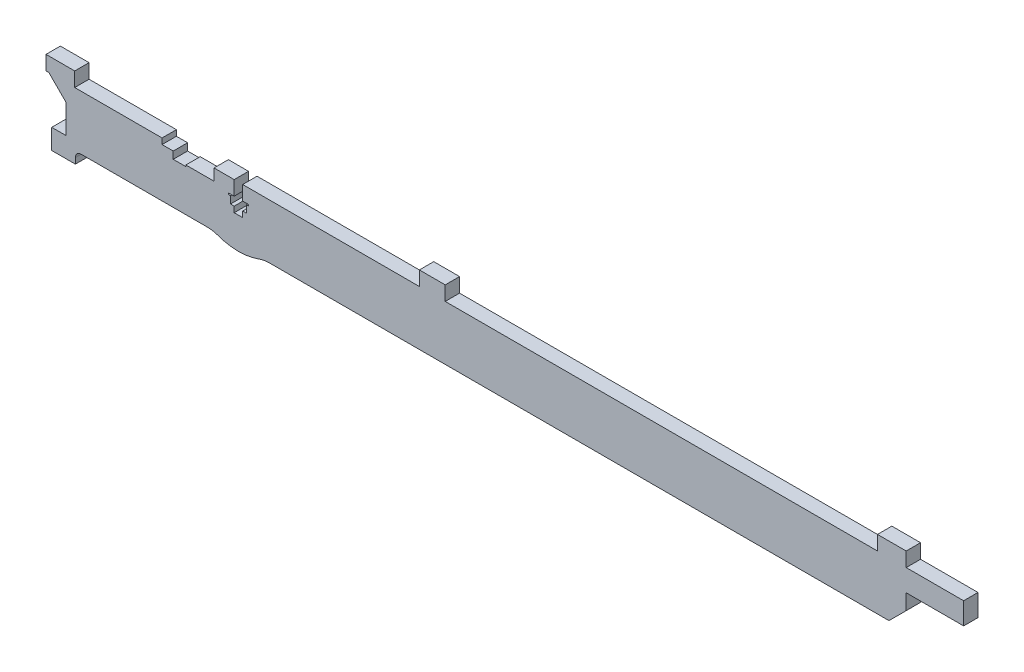
SolidWorks part; units mm, degrees
material "6061-T6 Black anodised"
ref_plane "Front Plane" through (0, 0, 0) normal (0, 0, 1) x (1, 0, 0)
ref_plane "Top Plane" through (0, 0, 0) normal (0, 1, 0) x (1, 0, 0)
ref_plane "Right Plane" through (0, 0, 0) normal (1, 0, 0) x (0, 0, -1)
sketch "Sketch1" plane through (0, 0, 0) normal (0, 0, 1) x (1, 0, 0)
  line L0 (-250.8, 3.6) -> (-241, 3.6)
  line L1 (0, 0) -> (20, 0)
  line L2 (-232.5, 8.6) -> (-232.5, -2.4) construction
  line L3 (0, 7.6) -> (20, 7.6)
  line L4 (20, 0) -> (20, 7.6)
  line L5 (-10, 7.6) -> (-160.5, 7.6)
  line L6 (0, 0) -> (0, -11.4)
  line L7 (0, -11.4) -> (-221.7995, -11.4)
  line L8 (-292.5, 1.6) -> (-292.5, -8.4)
  line L9 (-259.0932, 7.6) -> (-289.5, 7.6)
  line L10 (-299.5, 7.6) -> (-299.5, 12.6)
  line L11 (-299.5, 12.6) -> (-289.5, 12.6)
  line L12 (-289.5, 7.6) -> (-289.5, 12.6)
  line L13 (-169.5, 7.6) -> (-169.5, 12.6)
  line L14 (-250.8, 3.6) -> (-250.8, 3.1)
  line L15 (-250.8, 3.1) -> (-255.2, 3.1)
  line L16 (-255.2, 3.1) -> (-255.2, 5.6)
  line L17 (-255.2, 5.6) -> (-259.0932, 5.6)
  line L18 (0, 7.6) -> (0, 12.6)
  line L19 (0, 12.6) -> (-10, 12.6)
  line L20 (-10, 7.6) -> (-10, 12.6)
  line L21 (-259.0932, 5.6) -> (-259.0932, 7.6)
  line L22 (-255, 3.6) -> (-251, 3.6) construction
  line L23 (-255, 3.6) -> (-255, 13.6) construction
  line L24 (-251, 3.6) -> (-251, 13.6) construction
  line L25 (-255, 13.6) -> (-251, 13.6) construction
  line L26 (-255, 3.6) -> (-251, 13.6) construction
  line L27 (-271, 32.6) -> (-219.2068, 32.6) construction
  line L28 (-271, 32.6) -> (-271, 13.6) construction
  line L29 (-250, 33.6) -> (-250, 13.6) construction
  line L30 (-271, 13.6) -> (-250, 13.6) construction
  line L31 (-271, 32.6) -> (-250, 13.6) construction
  line L32 (-250, 33.6) -> (-271, 13.6) construction
  line L33 (-169.5, 12.6) -> (-160.5, 12.6)
  line L34 (-160.5, 12.6) -> (-160.5, 7.6)
  line L35 (-169.5, 7.6) -> (-231.02, 7.6)
  line L36 (-299.5, 7.6) -> (-298.5, 7.6)
  line L37 (-298.5, 7.6) -> (-292.5, 1.6)
  line L38 (-233.98, 7.6) -> (-233.98, 2.6)
  line L39 (-233.98, 2.6) -> (-236, 2.6)
  line L40 (-236, 2.6) -> (-236, 2.1)
  line L41 (-236, 2.1) -> (-235.25, 2.1)
  line L42 (-235.25, 2.1) -> (-235.25, -0.4)
  line L43 (-235.25, -0.4) -> (-233.98, -0.4)
  line L44 (-233.98, -0.4) -> (-233.98, -2.4)
  line L45 (-233.98, -2.4) -> (-231.02, -2.4)
  line L46 (-233.98, 7.6) -> (-241, 7.6)
  line L47 (-231.02, -0.4) -> (-231.02, -2.4)
  line L48 (-229.75, -0.4) -> (-231.02, -0.4)
  line L49 (-229.75, 2.1) -> (-229.75, -0.4)
  line L50 (-229, 2.1) -> (-229.75, 2.1)
  line L51 (-229, 2.6) -> (-229, 2.1)
  line L52 (-231.02, 2.6) -> (-229, 2.6)
  line L53 (-231.02, 7.6) -> (-231.02, 2.6)
  line L54 (-283, -20.0132) -> (-282, -18.2812)
  line L55 (-243.2005, -11.4) -> (-287.2708, -11.4)
  line L56 (-282, -15.4) -> (-287.2708, -15.4)
  line L57 (-251, 3.6) -> (-255, 13.6) construction
  line L58 (-282, -15.4) -> (-282, -18.2812)
  line L60 (-282, -30.9) -> (-297.5, -30.9)
  line L61 (-297.5, -30.9) -> (-297.5, -8.4)
  line L62 (-297.5, -8.4) -> (-292.5, -8.4)
  line L63 (-283, -25.7868) -> (-282, -27.5188)
  line L64 (-282, -23.9) -> (-282, -20.3633) construction
  line L65 (-283, -20.0132) -> (-286, -18.2812)
  line L66 (-286, -18.2812) -> (-290, -20.5906)
  line L67 (-290, -20.5906) -> (-290, -25.2094)
  line L68 (-290, -25.2094) -> (-286, -27.5188)
  line L69 (-286, -27.5188) -> (-283, -25.7868)
  line L70 (-282, -27.5188) -> (-282, -30.9)
  line L100 (-253, 8.6) -> (-238.8671, 8.6) construction
  line L116 (-241, 7.6) -> (-241, 3.6)
  arc A0 (-287.2708, -11.4) -> (-287.2708, -15.4) centre (-287.2708, -13.4) ccw
  circle A1 centre (-286, -22.9) radius 4 construction
  arc A2 (-221.7995, -11.4) -> (-225.2612, -12.0183) centre (-221.7995, -21.4) ccw
  arc A4 (-243.2005, -11.4) -> (-239.7388, -12.0183) centre (-243.2005, -21.4) cw
  arc A5 (-239.7388, -12.0183) -> (-225.2612, -12.0183) centre (-232.5, 7.6) ccw
  point P27 (-253, 8.6)
  point P130 (-242, 8.6)
  dimension "D21" = 0.5
  dimension "D24" = 0.5
  dimension "D26" = 2
  dimension "D34" = 8
  dimension "D35" = 2
  dimension "D39" = 10
  dimension "D40" = 9
  dimension "D2" = 20
  dimension "D3" = 7.6
  dimension "D4" = 5
  dimension "D5" = 11.4
  dimension "D6" = 1
  dimension "D7" = 10
  dimension "D8" = 6
  dimension "D9" = 6
  dimension "D10" = 6
  dimension "D11" = 4
  dimension "D12" = 9
  dimension "D13" = 189.5
  dimension "D14" = 10
  dimension "D15" = 4
  dimension "D16" = 1
  dimension "D17" = 8.5
  dimension "D18" = 20
  dimension "D19" = 42.5
  dimension "D20" = 25
  dimension "D22" = 0.2
  dimension "D23" = 0.2
  dimension "D25" = 2.5
  dimension "D27" = 2.96
  dimension "D28" = 11
  dimension "D29" = 7
  dimension "D30" = 5.5
  dimension "D31" = 270
  dimension "D32" = 11.5
  dimension "D33" = 6.5
  dimension "D36" = 5
  dimension "D37" = 8
  dimension "D38" = 16
  dimension "D45" = 1
extrude "Boss-Extrude1" add sketch "Sketch1" along normal blind 5
chamfer "Chamfer1" distance 6 angle 45 1 edges at (0, -11.4, 2.5)
chamfer "Chamfer2" [suppressed] distance 2.6 angle 60
sketch "Sketch2" plane through (-241, 0, 0) normal (-1, 0, 0) x (0, 0, 1)
  line L0 (5, 5.6) -> (2, 5.6) construction
  line L1 (5, 7.6) -> (5, 3.6) construction
  line L2 (2, 6.475) -> (2, 5.6) construction
  circle A0 centre (2, 5.6) radius 0.4645
extrude "Cut-Extrude1" [suppressed] cut sketch "Sketch2" against normal blind 0.5
sketch "Sketch3" plane through (0, 0, 5) normal (0, 0, 1) x (1, 0, 0)
  line L0 (-289.2708, -13.4) -> (-289.2708, -15.4)
  line L1 (-289.2708, -15.4) -> (-297.5, -15.4)
  line L2 (-282, -13.4) -> (-282, -30.9)
  line L3 (-282, -30.9) -> (-297.5, -30.9)
  line L4 (-297.5, -15.4) -> (-297.5, -30.9)
  line L5 (-289.2708, -13.4) -> (-282, -13.4)
  arc A0 (-287.2708, -11.4) -> (-287.2708, -15.4) centre (-287.2708, -13.4) ccw construction
extrude "Cut-Extrude2" cut sketch "Sketch3" against normal through all
equation "\"y-plate-thickness\"=5"
equation "\"bed-plate-thickness\"=3"
equation "\"x-plate-thickness\"=5"
equation "\"rod-diameter\"=12"
equation "\"D4@Sketch1\"=\"x-plate-thickness\""
equation "\"D1@Boss-Extrude1\"=\"x-plate-thickness\""
